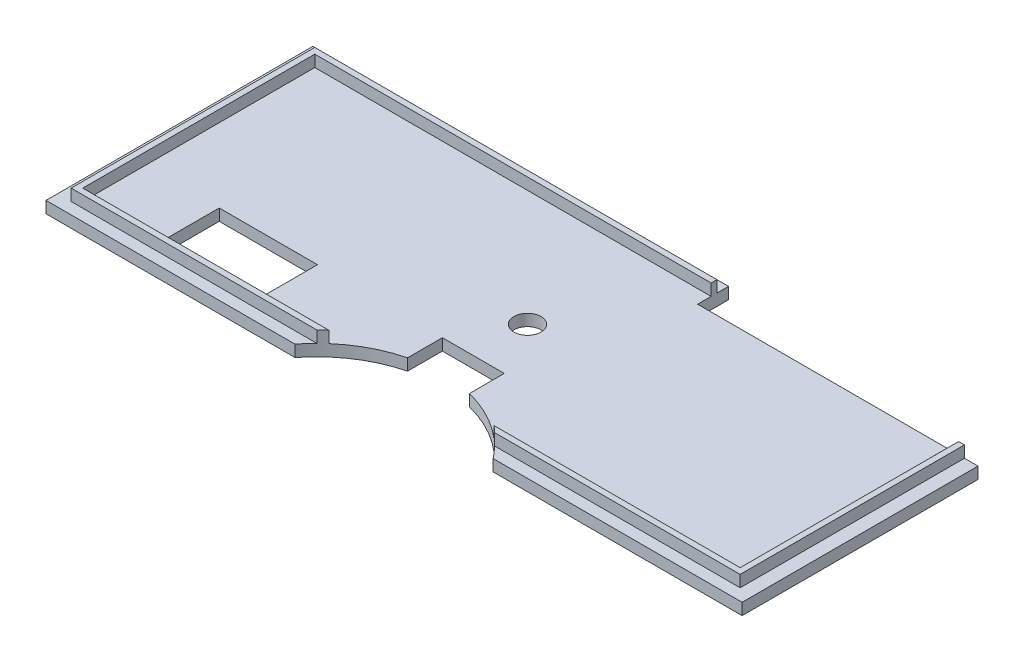
SolidWorks part; units mm, degrees
ref_plane "Front Plane" through (0, 0, 0) normal (0, 0, 1) x (1, 0, 0)
ref_plane "Top Plane" through (0, 0, 0) normal (0, 1, 0) x (1, 0, 0)
ref_plane "Right Plane" through (0, 0, 0) normal (1, 0, 0) x (0, 0, -1)
sketch "Sketch2" plane through (0, 0, 0) normal (0, 1, 0) x (1, 0, 0)
  line L1 (90, 34.5) -> (-90, 34.5)
  line L2 (90, 34.5) -> (90, -34.5)
  line L3 (90, -34.5) -> (-90, -34.5)
  line L4 (-90, 34.5) -> (-90, -34.5)
  line L5 (90, 34.5) -> (-90, -34.5) construction
  line L6 (90, -34.5) -> (-90, 34.5) construction
  point P0 (0, 0)
  dimension "D1" = 180
  dimension "D2" = 69
extrude "Boss-Extrude1" add sketch "Sketch2" along normal blind 3
sketch "Sketch3" plane through (0, 3, 0) normal (0, 1, 0) x (1, 0, 0)
  line L1 (86.5, 31.5) -> (-86.5, 31.5)
  line L2 (86.5, 31.5) -> (86.5, -31.5)
  line L3 (86.5, -31.5) -> (-86.5, -31.5)
  line L4 (-86.5, 31.5) -> (-86.5, -31.5)
  line L5 (86.5, 31.5) -> (-86.5, -31.5) construction
  line L6 (86.5, -31.5) -> (-86.5, 31.5) construction
  line L7 (85, 30) -> (-85, 30)
  line L8 (85, 30) -> (85, -30)
  line L9 (85, -30) -> (-85, -30)
  line L10 (-85, 30) -> (-85, -30)
  line L11 (85, 30) -> (-85, -30) construction
  line L12 (85, -30) -> (-85, 30) construction
  point P0 (0, 0)
  point P6 (0, 0)
  dimension "D1" = 173
  dimension "D2" = 63
  dimension "D3" = 170
  dimension "D4" = 60
extrude "Boss-Extrude2" add sketch "Sketch3" along normal blind 3
sketch "Sketch4" plane through (0, 0, 0) normal (0, -1, 0) x (1, 0, 0)
  line L0 (-90, 34.5) -> (90, 34.5) construction
  line L1 (-65.9, 34.5) -> (-40.5, 34.5)
  line L2 (-65.9, 34.5) -> (-65.9, 9.1)
  line L3 (-65.9, 9.1) -> (-40.5, 9.1)
  line L4 (-40.5, 34.5) -> (-40.5, 9.1)
  line L5 (-90, -34.5) -> (-90, 34.5) construction
  line L6 (-40.5, 21.8) -> (-65.9, 21.8) construction
  line L8 (-40.5, 13.8) -> (-65.9, 13.8)
  line L9 (-40.5, 13.8) -> (-40.5, 29.8)
  line L10 (-40.5, 29.8) -> (-65.9, 29.8)
  line L11 (-65.9, 13.8) -> (-65.9, 29.8)
  line L12 (-40.5, 13.8) -> (-65.9, 29.8) construction
  line L13 (-40.5, 29.8) -> (-65.9, 13.8) construction
  point P10 (-53.2, 21.8)
  dimension "D1" = 49.5
  dimension "D2" = 25.4
  dimension "D3" = 25.4
  dimension "D4" = 16
extrude "Cut-Extrude1" cut sketch "Sketch4" against normal blind 10 contours L4 L10 L2 L8 region at (-53.2, 0, 21.8)
sketch "Sketch5" plane through (0, 6, 0) normal (0, 1, 0) x (1, 0, 0)
  line L0 (85, 30) -> (-85, 30) construction
  line L1 (86.5, 31.5) -> (17.5, 31.5)
  line L2 (86.5, 31.5) -> (86.5, 30)
  line L3 (86.5, 30) -> (17.5, 30)
  line L4 (17.5, 31.5) -> (17.5, 30)
  dimension "D1" = 69
extrude "Cut-Extrude2" cut sketch "Sketch5" against normal blind 3
sketch "Sketch6" plane through (0, 6, 0) normal (0, 1, 0) x (1, 0, 0)
  line L0 (85, -30) -> (85, 30) construction
  line L1 (86.5, 30) -> (85, 30)
  line L2 (86.5, 30) -> (86.5, 26.5)
  line L3 (86.5, 26.5) -> (85, 26.5)
  line L4 (85, 30) -> (85, 26.5)
  dimension "D1" = 3.5
extrude "Cut-Extrude3" cut sketch "Sketch6" against normal blind 3
sketch "Sketch7" plane through (0, 0, 0) normal (0, -1, 0) x (1, 0, 0)
  line L0 (0, 34.5) -> (0, -34.5) construction
  line L1 (-90, 34.5) -> (90, 34.5) construction
  line L2 (90, -34.5) -> (-90, -34.5) construction
  circle A0 centre (0, 0) radius 3.5
  dimension "D1" = 7
extrude "Cut-Extrude4" cut sketch "Sketch7" against normal blind 3
sketch "Sketch8" plane through (0, 0, 0) normal (0, -1, 0) x (1, 0, 0)
  line L0 (0, 34.5) -> (0, 54.5) construction
  line L1 (-90, 34.5) -> (90, 34.5) construction
  circle A0 centre (0, 54.5) radius 32.5
  dimension "D2" = 65
  dimension "D1" = 20
extrude "Cut-Extrude5" cut sketch "Sketch8" against normal blind 10
sketch "Sketch9" plane through (0, 0, 0) normal (0, -1, 0) x (1, 0, 0)
  line L1 (8, 30) -> (-8, 30)
  line L2 (8, 30) -> (8, 14)
  line L3 (8, 14) -> (-8, 14)
  line L4 (-8, 30) -> (-8, 14)
  line L5 (8, 30) -> (-8, 14) construction
  line L6 (8, 14) -> (-8, 30) construction
  arc A0 (-25.6174, 34.5) -> (25.6174, 34.5) centre (0, 54.5) ccw construction
  point P0 (0, 22)
  dimension "D1" = 16
  dimension "D2" = 16
extrude "Cut-Extrude6" cut sketch "Sketch9" against normal blind 10
sketch "Sketch10" plane through (0, 3, 0) normal (0, 1, 0) x (1, 0, 0)
  line L0 (17.5, 31.5) -> (17.5, 30) construction
  line L1 (90, 34.5) -> (17.5, 34.5)
  line L2 (90, 34.5) -> (90, 26.5)
  line L3 (90, 26.5) -> (17.5, 26.5)
  line L4 (17.5, 34.5) -> (17.5, 26.5)
  line L5 (85, 26.5) -> (86.5, 26.5) construction
  point P5 (17.5, 30.5)
  dimension "D1" = 0
  dimension "D2" = 0
extrude "Cut-Extrude7" cut sketch "Sketch10" against normal blind 10
